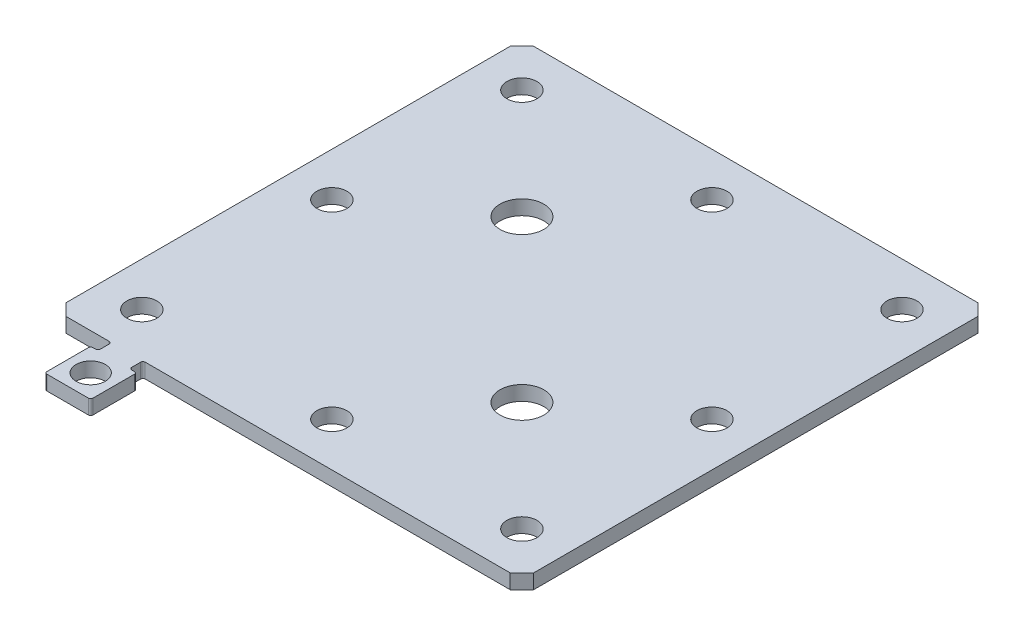
SolidWorks part; units mm, degrees
material "TIMETAL 35A CP Titanium (ASTM Grade 1) 99.1 Ti"
ref_plane "Front Plane" through (0, 0, 0) normal (0, 0, 1) x (1, 0, 0)
ref_plane "Top Plane" through (0, 0, 0) normal (0, 1, 0) x (1, 0, 0)
ref_plane "Right Plane" through (0, 0, 0) normal (1, 0, 0) x (0, 0, -1)
sketch "Sketch1" plane through (0, 0, 0) normal (0, 1, 0) x (1, 0, 0)
  line L0 (-51.4236, 48.8836) -> (-48.8836, 51.4236)
  line L1 (-48.8836, -50.1764) -> (-38.9611, -50.1764)
  line L2 (-51.4236, -47.6364) -> (-51.4236, 48.8836)
  line L3 (-48.8836, 51.4236) -> (47.6364, 51.4236)
  line L4 (50.1764, -47.6364) -> (50.1764, 48.8836)
  line L5 (-51.4236, -50.1764) -> (50.1764, 51.4236) construction
  line L6 (-51.4236, 51.4236) -> (50.1764, -50.1764) construction
  line L7 (47.6364, 51.4236) -> (50.1764, 48.8836)
  line L8 (47.6364, -50.1764) -> (50.1764, -47.6364)
  line L9 (-51.4236, -47.6364) -> (-48.8836, -50.1764)
  line L10 (-41.8986, 41.8986) -> (-0.6236, 41.8986)
  line L11 (40.6514, -40.6514) -> (-41.8986, -40.6514) construction
  line L12 (40.6514, -40.6514) -> (40.6514, 41.8986) construction
  line L13 (40.6514, 41.8986) -> (-41.8986, 41.8986) construction
  line L14 (-41.8986, -40.6514) -> (-41.8986, 41.8986) construction
  line L15 (40.6514, -40.6514) -> (-41.8986, 41.8986) construction
  line L16 (40.6514, 41.8986) -> (-41.8986, -40.6514) construction
  line L17 (40.6514, -40.6514) -> (-0.6236, -40.6514)
  line L18 (-35.5486, -34.3014) -> (34.3014, -34.3014)
  line L19 (-35.5486, -34.3014) -> (-35.5486, 35.5486)
  line L20 (-35.5486, 35.5486) -> (34.3014, 35.5486)
  line L21 (34.3014, -34.3014) -> (34.3014, 35.5486)
  line L22 (-35.5486, -34.3014) -> (34.3014, 35.5486) construction
  line L23 (-35.5486, 35.5486) -> (34.3014, -34.3014) construction
  line L24 (-35.5486, -53.1144) -> (-35.5486, -63.1144) construction
  line L25 (-40.5486, -53.1144) -> (-38.9611, -53.1144)
  line L26 (-40.5486, -53.1144) -> (-40.5486, -63.1144)
  line L27 (-40.5486, -63.1144) -> (-30.5486, -63.1144)
  line L28 (-30.5486, -53.1144) -> (-30.5486, -63.1144)
  line L29 (-38.9611, -53.1144) -> (-38.9611, -50.1764)
  line L30 (-32.1361, -53.1144) -> (-32.1361, -50.1764)
  line L31 (-32.1361, -53.1144) -> (-30.5486, -53.1144)
  line L32 (-32.1361, -50.1764) -> (47.6364, -50.1764)
  circle A0 centre (-41.8986, 41.8986) radius 3.2639
  circle A1 centre (-0.6236, 41.8986) radius 3.2639
  circle A2 centre (40.6514, 41.8986) radius 3.2639
  circle A3 centre (40.6514, 0.6236) radius 3.2639
  circle A4 centre (40.6514, -40.6514) radius 3.2639
  circle A5 centre (-0.6236, -40.6514) radius 3.2639
  circle A6 centre (-41.8986, -40.6514) radius 3.2639
  circle A7 centre (-41.8986, 0.6236) radius 3.2639
  circle A8 centre (-21.2611, 41.8986) radius 4.7625 construction
  circle A9 centre (20.0139, -40.6514) radius 4.7625 construction
  point P0 (-0.6236, 0.6236)
  point P13 (-0.6236, 0.6236)
  point P34 (-0.6236, 0.6236)
  dimension "D13" = 6.5278
  dimension "D14" = 9.525
  dimension "D1" = 101.6
  dimension "D2" = 101.6
  dimension "D3" = 2.54
  dimension "D4" = 2.54
  dimension "D5" = 2.54
  dimension "D6" = 2.54
  dimension "D7" = 2.54
  dimension "D8" = 2.54
  dimension "D9" = 2.54
  dimension "D10" = 2.54
  dimension "D11" = 82.55
  dimension "D12" = 82.55
  dimension "D15" = 69.85
  dimension "D16" = 69.85
  dimension "D17" = 10
  dimension "D18" = 10
  dimension "D19" = 1.5875
extrude "Boss-Extrude1" add sketch "Sketch1" along normal blind 3.175 contours L2 L9 L1 L8 L4 L7 L3 L0 A9 A4 A5 A8 A1 A0 A7 A6 A3 A2 L21 L18 L19 L20 | L18 L21 L20 L19 region at (-49.071, 0, -49.071) region at (-0.6236, 0, -0.6236)
fillet "Fillet1" radius 0.5 8 edges at (-40.5486, 1.5875, 63.1144) (-30.5486, 1.5875, 63.1144) (-30.5486, 1.5875, 53.1144) (-32.1361, 1.5875, 53.1144) (-32.1361, 1.5875, 50.1764) (-40.5486, 1.5875, 53.1144) (-38.9611, 1.5875, 53.1144) (-38.9611, 1.5875, 50.1764)
sketch "Sketch2" plane through (0, 3.175, 0) normal (0, 1, 0) x (1, 0, 0)
  line L0 (-51.4236, 18.0861) -> (-18.0861, 18.0861) construction
  line L1 (-18.0861, 18.0861) -> (-18.0861, 51.4236) construction
  line L2 (16.8389, -50.1764) -> (16.8389, -16.8389) construction
  line L3 (16.8389, -16.8389) -> (50.1764, -16.8389) construction
  line L4 (-40.0486, -53.6144) -> (-31.0486, -62.6144) construction
  line L5 (-31.0486, -53.6144) -> (-40.0486, -62.6144) construction
  line L16 (-40.5486, -53.6144) -> (-40.5486, -62.6144)
  line L17 (-40.0486, -63.1144) -> (-31.0486, -63.1144)
  line L18 (-30.5486, -62.6144) -> (-30.5486, -53.6144)
  line L19 (-31.0486, -53.1144) -> (-31.6361, -53.1144)
  line L20 (-32.1361, -52.6144) -> (-32.1361, -50.6764)
  line L21 (-31.6361, -50.1764) -> (47.6364, -50.1764)
  line L22 (47.6364, -50.1764) -> (50.1764, -47.6364)
  line L23 (50.1764, -47.6364) -> (50.1764, 48.8836)
  line L24 (50.1764, 48.8836) -> (47.6364, 51.4236)
  line L25 (47.6364, 51.4236) -> (-48.8836, 51.4236)
  line L26 (-48.8836, 51.4236) -> (-51.4236, 48.8836)
  line L27 (-51.4236, 48.8836) -> (-51.4236, -47.6364)
  line L28 (-51.4236, -47.6364) -> (-48.8836, -50.1764)
  line L29 (-48.8836, -50.1764) -> (-39.4611, -50.1764)
  line L30 (-38.9611, -50.6764) -> (-38.9611, -52.6144)
  line L31 (-39.4611, -53.1144) -> (-40.0486, -53.1144)
  line L32 (-40.5486, -53.6144) -> (-40.5486, -62.6144)
  line L33 (-40.0486, -63.1144) -> (-31.0486, -63.1144)
  line L34 (-30.5486, -62.6144) -> (-30.5486, -53.6144)
  line L35 (-31.0486, -53.1144) -> (-31.6361, -53.1144)
  line L36 (-32.1361, -52.6144) -> (-32.1361, -50.6764)
  line L37 (-31.6361, -50.1764) -> (47.6364, -50.1764)
  line L38 (47.6364, -50.1764) -> (50.1764, -47.6364)
  line L39 (50.1764, -47.6364) -> (50.1764, 48.8836)
  line L40 (50.1764, 48.8836) -> (47.6364, 51.4236)
  line L41 (47.6364, 51.4236) -> (-48.8836, 51.4236)
  line L42 (-48.8836, 51.4236) -> (-51.4236, 48.8836)
  line L43 (-51.4236, 48.8836) -> (-51.4236, -47.6364)
  line L44 (-51.4236, -47.6364) -> (-48.8836, -50.1764)
  line L45 (-48.8836, -50.1764) -> (-39.4611, -50.1764)
  line L46 (-38.9611, -50.6764) -> (-38.9611, -52.6144)
  line L47 (-39.4611, -53.1144) -> (-40.0486, -53.1144)
  circle A0 centre (-41.8986, 41.8986) radius 3.2639 construction
  circle A1 centre (-35.5486, -58.1144) radius 3.175
  circle A2 centre (-0.6236, 41.8986) radius 3.2639 construction
  circle A3 centre (40.6514, 41.8986) radius 3.2639 construction
  circle A4 centre (40.6514, 0.6236) radius 3.2639 construction
  circle A5 centre (40.6514, -40.6514) radius 3.2639 construction
  circle A6 centre (-0.6236, -40.6514) radius 3.2639 construction
  circle A7 centre (-41.8986, -40.6514) radius 3.2639 construction
  arc A8 (-40.5486, -62.6144) -> (-40.0486, -63.1144) centre (-40.0486, -62.6144) ccw
  arc A9 (-31.0486, -63.1144) -> (-30.5486, -62.6144) centre (-31.0486, -62.6144) ccw
  arc A10 (-30.5486, -53.6144) -> (-31.0486, -53.1144) centre (-31.0486, -53.6144) ccw
  arc A11 (-32.1361, -52.6144) -> (-31.6361, -53.1144) centre (-31.6361, -52.6144) ccw
  arc A12 (-31.6361, -50.1764) -> (-32.1361, -50.6764) centre (-31.6361, -50.6764) ccw
  arc A13 (-38.9611, -50.6764) -> (-39.4611, -50.1764) centre (-39.4611, -50.6764) ccw
  arc A14 (-39.4611, -53.1144) -> (-38.9611, -52.6144) centre (-39.4611, -52.6144) ccw
  arc A15 (-40.0486, -53.1144) -> (-40.5486, -53.6144) centre (-40.0486, -53.6144) ccw
  arc A16 (-40.5486, -62.6144) -> (-40.0486, -63.1144) centre (-40.0486, -62.6144) ccw
  arc A17 (-31.0486, -63.1144) -> (-30.5486, -62.6144) centre (-31.0486, -62.6144) ccw
  arc A18 (-30.5486, -53.6144) -> (-31.0486, -53.1144) centre (-31.0486, -53.6144) ccw
  arc A19 (-32.1361, -52.6144) -> (-31.6361, -53.1144) centre (-31.6361, -52.6144) ccw
  arc A20 (-31.6361, -50.1764) -> (-32.1361, -50.6764) centre (-31.6361, -50.6764) ccw
  arc A21 (-38.9611, -50.6764) -> (-39.4611, -50.1764) centre (-39.4611, -50.6764) ccw
  arc A22 (-39.4611, -53.1144) -> (-38.9611, -52.6144) centre (-39.4611, -52.6144) ccw
  arc A23 (-40.0486, -53.1144) -> (-40.5486, -53.6144) centre (-40.0486, -53.6144) ccw
  circle A24 centre (-41.8986, 0.6236) radius 3.2639 construction
  circle A25 centre (-41.8986, 0.6236) radius 3.2639
  circle A26 centre (-41.8986, -40.6514) radius 3.2639
  circle A27 centre (-0.6236, -40.6514) radius 3.2639
  circle A28 centre (40.6514, -40.6514) radius 3.2639
  circle A29 centre (40.6514, 0.6236) radius 3.2639
  circle A30 centre (40.6514, 41.8986) radius 3.2639
  circle A31 centre (-0.6236, 41.8986) radius 3.2639
  circle A33 centre (-41.8986, 41.8986) radius 3.2639
  circle A34 centre (-18.0861, 18.0861) radius 4.7625
  circle A35 centre (16.8389, -16.8389) radius 4.7625
  dimension "D6" = 9.525
  dimension "D7" = 9.525
  dimension "D8" = 6.35
  dimension "D2" = 33.3375
  dimension "D3" = 33.3375
  dimension "D4" = 33.3375
  dimension "D5" = 33.3375
  dimension "D1" = 0
extrude "Cut-Extrude2" cut sketch "Sketch2" against normal through all contours A34 | A35 | A1
